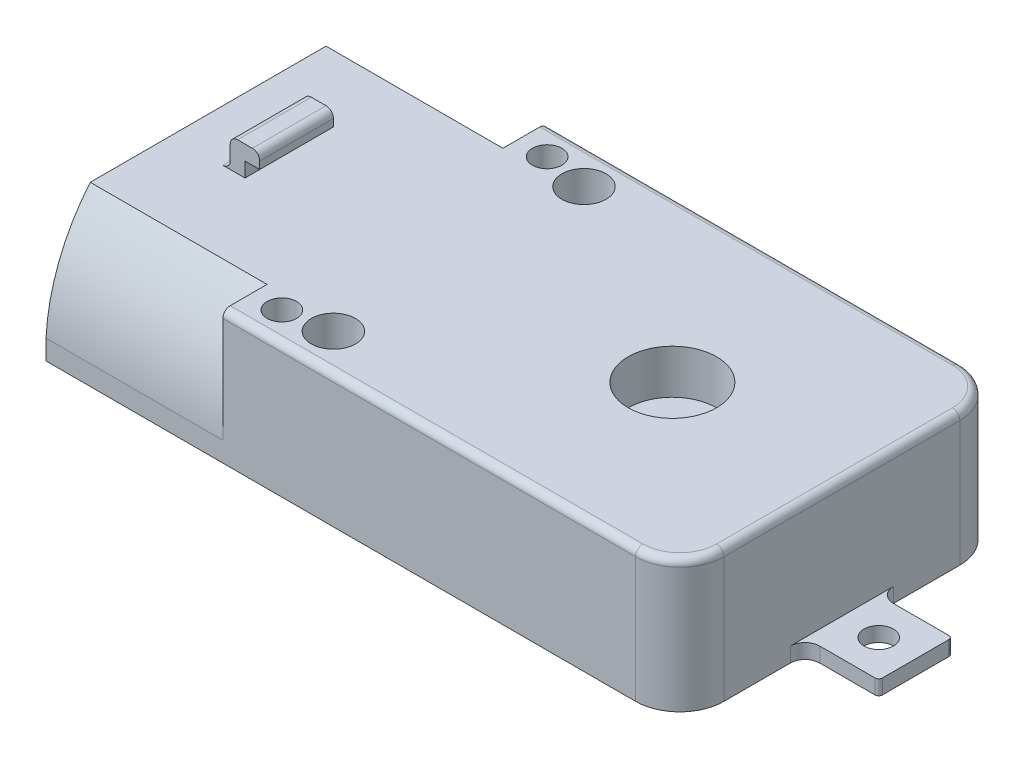
SolidWorks part; units mm, degrees
ref_plane "Front Plane" through (0, 0, 0) normal (0, 0, 1) x (1, 0, 0)
ref_plane "Top Plane" through (0, 0, 0) normal (0, 1, 0) x (1, 0, 0)
ref_plane "Right Plane" through (0, 0, 0) normal (1, 0, 0) x (0, 0, -1)
sketch "Sketch2" plane through (0, 0, 0) normal (0, 1, 0) x (1, 0, 0)
  line L0 (31, 11) -> (0, 11) construction
  line L1 (0, 0) -> (31, 0)
  line L2 (0, 0) -> (0, 22)
  line L3 (0, 22) -> (31, 22)
  line L4 (31, 0) -> (31, 22)
  line L7 (31, 8.5) -> (31, 13.5)
  dimension "48" = 31
  dimension "22" = 22
extrude "Boss-Extrude2" add sketch "Sketch2" along normal blind 9 contours L0 L7 L4 L3 L2 | L4 L0 L2 L1 region at (15.5, 0, -5.5) region at (15.5, 0, -16.5)
sketch "Sketch4" plane through (31, 0, 0) normal (1, 0, 0) x (0, 0, -1)
  line L0 (0, 0) -> (22, 0) construction
  line L1 (8.5, 0) -> (13.5, 0)
  line L2 (8.5, 0) -> (8.5, 1)
  line L3 (8.5, 1) -> (13.5, 1)
  line L4 (13.5, 0) -> (13.5, 1)
  point P6 (11, 1)
  dimension "D1" = 1
  dimension "D2" = 5
  dimension "D3" = 11
extrude "Boss-Extrude3" add sketch "Sketch4" along normal blind 5
sketch "Sketch5" plane through (0, 1, 0) normal (0, 1, 0) x (1, 0, 0)
  circle A0 centre (33.5, 11) radius 1
  dimension "D1" = 2
  dimension "D2" = 2.5
  dimension "D3" = 2.5
extrude "Cut-Extrude1" cut sketch "Sketch5" against normal blind 5
fillet "Fillet1" radius 1 1 edges
fillet "Fillet2" radius 1 1 edges
fillet "Fillet3" radius 3 1 edges at (31, 4.5, 0)
fillet "Fillet4" radius 3 1 edges at (31, 4.5, -22)
sketch "Sketch6" plane through (0, 0, 0) normal (-1, 0, 0) x (0, 0, 1)
  line L0 (-11, 0) -> (-11, 9) construction
  line L1 (0, 0) -> (-22, 0) construction
  line L2 (0, 9) -> (-22, 9) construction
  line L3 (-22, 0) -> (0, 0)
  line L5 (-22, 0) -> (-22.0206, -0.0102)
  line L6 (0, 1.3449) -> (0, 0)
  line L7 (-19, 9) -> (-3, 9)
  line L8 (0, 0) -> (-22, 0)
  arc A0 (0, 0) -> (-3, 9) centre (-12.9826, 0.6725) ccw
  arc A1 (-22, 0) -> (-19, 9) centre (-9.0174, 0.6725) cw
  point P9 (0, 0)
  line M1 (-22, 0) -> (0, 0)
  line M2 (0, 0) -> (0, 9)
  line M3 (0, 9) -> (-22, 9)
  line M4 (-22, 9) -> (-22, 0)
  dimension "D1" = 13
  dimension "D2" = 3
sketch "Sketch7" plane through (0, 0, 0) normal (-1, 0, 0) x (0, 0, 1)
extrude "Boss-Extrude4" add sketch "Sketch6" along normal blind 12 contours L0 L7 A1 M1 M4 | L0 L8 A0 M2 M3 region at (0, 4.2857, -16.1047) region at (0, 4.2857, -5.8953)
fillet "Fillet5" radius 0.5 5 edges at (14, 9, -22) (30.1213, 9, -21.1213) (31, 9, -11) (30.1213, 9, -0.8787) (14, 9, 0)
fillet "Fillet6" radius 0.25 2 edges at (36, 0.5, -13.5) (36, 0.5, -8.5)
sketch "Sketch8" plane through (0, 9, 0) normal (0, 1, 0) x (1, 0, 0)
  line L0 (30.5, 3) -> (30.5, 19) construction
  circle A0 centre (19.5, 11) radius 3
  point P2 (30.5, 11)
  dimension "D1" = 6
  dimension "D2" = 11
extrude "Cut-Extrude3" cut sketch "Sketch8" against normal blind 3
sketch "Sketch9" plane through (0, 6, 0) normal (0, 1, 0) x (1, 0, 0)
  circle A0 centre (19.5, 11) radius 0.75
  dimension "1,5" = 1.5
extrude "Cut-Extrude4" cut sketch "Sketch9" against normal blind 3
sketch "Sketch10" plane through (0, 9, 0) normal (0, 1, 0) x (1, 0, 0)
  line L0 (-12, 11) -> (30.5, 11) construction
  line L1 (-12, 3) -> (-12, 19) construction
  line L2 (30.5, 3) -> (30.5, 19) construction
  line L4 (28, 0) -> (0, 0) construction
  circle A0 centre (5, 19.5) radius 1.5
  circle A1 centre (5, 2.5) radius 1.5
  dimension "D1" = 3
  dimension "2,5" = 2.5
  dimension "5" = 5
extrude "Cut-Extrude7" cut sketch "Sketch10" against normal through all
sketch "Sketch12" plane through (0, 9, 0) normal (0, 1, 0) x (1, 0, 0)
  line L0 (28, 0) -> (0, 0) construction
  circle A0 centre (2, 2) radius 1
  circle A1 centre (2, 20) radius 1
  dimension "D1" = 2
  dimension "D2" = 2
  dimension "D3" = 2
  dimension "D4" = 2
  dimension "D5" = 2
  dimension "D6" = 2
extrude "Cut-Extrude8" cut sketch "Sketch12" against normal blind 5
sketch "Sketch13" plane through (0, 9, 0) normal (0, 1, 0) x (1, 0, 0)
  line L0 (-12, 11) -> (36, 11) construction
  line L1 (-8, 13.5) -> (-7, 13.5)
  line L2 (-8, 13.5) -> (-8, 8.5)
  line L3 (-8, 8.5) -> (-7, 8.5)
  line L4 (-7, 13.5) -> (-7, 8.5)
  line L5 (-12, 3) -> (-12, 19) construction
  line L6 (36, 13.25) -> (36, 8.75) construction
  dimension "D1" = 4
  dimension "D2" = 1
  dimension "D3" = 5
  dimension "D4" = 2.5
extrude "Boss-Extrude5" add sketch "Sketch13" along normal blind 2
sketch "Sketch14" plane through (-7, 0, 0) normal (1, 0, 0) x (0, 0, -1)
  line L0 (13.5, 11) -> (13.5, 9) construction
  line L1 (8.5, 11) -> (13.5, 11)
  line L2 (8.5, 11) -> (8.5, 10)
  line L3 (8.5, 10) -> (13.5, 10)
  line L4 (13.5, 11) -> (13.5, 10)
extrude "Boss-Extrude6" add sketch "Sketch14" along normal blind 1
fillet "Fillet7" radius 0.5 1 edges at (-8, 11, -11)
fillet "Fillet8" radius 0.5 1 edges at (-8, 9, -11)
fillet "Fillet9" radius 0.5 1 edges at (-6, 11, -11)
sketch "Sketch16" plane through (-12, 0, 0) normal (-1, 0, 0) x (0, 0, 1)
  line L0 (-18.2321, 8.3594) -> (-3.7679, 8.3594)
  line L1 (-21.0013, 1.2932) -> (-21, 0)
  line L2 (-0.9987, 1.2932) -> (-0.9987, 0)
  line L3 (-21, 0) -> (-0.9987, 0)
  arc A2 (-18.2321, 8.3594) -> (-21.0013, 1.2932) centre (-9.0174, 0.6725) ccw
  arc A3 (-18.2321, 8.3594) -> (-21.0013, 1.2932) centre (-9.0174, 0.6725) ccw
  arc A5 (-0.9987, 1.2932) -> (-3.7679, 8.3594) centre (-12.9826, 0.6725) ccw
  arc A6 (-0.9987, 1.2932) -> (-3.7679, 8.3594) centre (-12.9826, 0.6725) ccw
  dimension "D1" = 1
  dimension "D2" = 1
extrude "Cut-Extrude9" cut sketch "Sketch16" against normal blind 10
